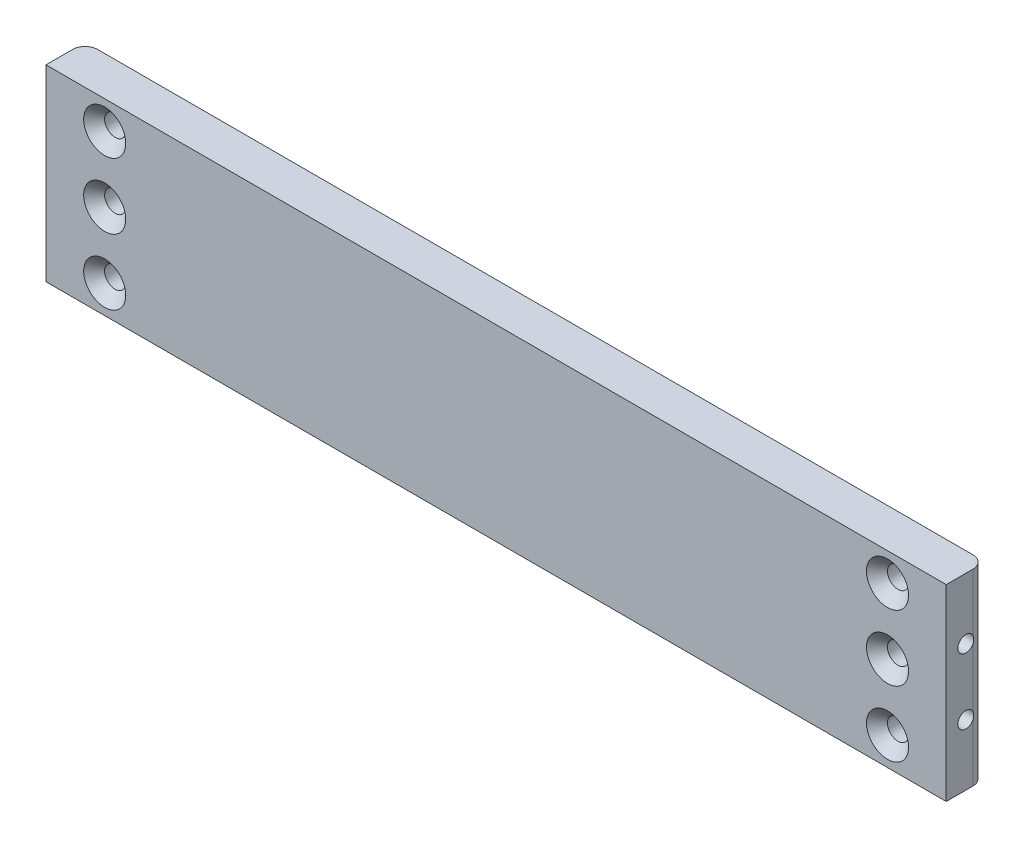
SolidWorks part; units mm, degrees
material "7075-T6 (SN)"
ref_plane "Plano frontal" through (0, 0, 0) normal (0, 0, 1) x (1, 0, 0)
ref_plane "Plano superior" through (0, 0, 0) normal (0, 1, 0) x (1, 0, 0)
ref_plane "Plano direito" through (0, 0, 0) normal (1, 0, 0) x (0, 0, -1)
sketch "Esboço1" plane through (0, 0, 0) normal (0, 0, 1) x (1, 0, 0)
  line L0 (-25, 120) -> (500, 120)
  line L1 (0, 0) -> (475, 0) construction
  line L2 (0, 0) -> (0, 120) construction
  line L3 (0, 120) -> (475, 120) construction
  line L4 (475, 0) -> (475, 120) construction
  line L5 (500, 120) -> (500, 0) construction
  line L6 (500, 0) -> (-25, 0)
  line L7 (-25, 0) -> (-25, 120) construction
  line L8 (237.5, 120) -> (237.5, 0) construction
  line L9 (-12.5, 102) -> (-12.5, 120) construction
  line L10 (-12.5, 18) -> (-12.5, 0) construction
  line L11 (-25, 120) -> (0, 120) construction
  line L12 (-25, 120) -> (0, 120) construction
  line L13 (-25, 60) -> (0, 60) construction
  line L14 (-25, 120) -> (-50, 120)
  line L15 (-50, 120) -> (-50, 0)
  line L16 (-50, 0) -> (-25, 0)
  line L17 (525, 0) -> (500, 0)
  line L18 (525, 120) -> (525, 0)
  line L19 (500, 120) -> (525, 120)
  circle A0 centre (-12.5, 102) radius 6
  circle A1 centre (-12.5, 60) radius 6
  circle A2 centre (-12.5, 18) radius 6
  circle A3 centre (487.5, 102) radius 6
  circle A4 centre (487.5, 60) radius 6
  circle A5 centre (487.5, 18) radius 6
  point P16 (-25, 60)
  point P23 (-12.5, 60)
  point P33 (0, 0)
  dimension "D5" = 12
  dimension "D1" = 525
  dimension "D2" = 120
  dimension "D3" = 25
  dimension "D4" = 25
  dimension "D6" = 18
  dimension "D7" = 25
extrude "Ressalto-extrusão1" add sketch "Esboço1" along normal blind 25 contours L0 L19 L18 L17 L6 L16 L15 L14
hole_wizard "Escareado para parafuso Allen sextavado escareado de M121" positions "Esboço2" profile "Esboço3" countersink size "M12" standard "ISO"
sketch "Esboço2" plane through (0, 0, 25) normal (0, 0, 1) x (1, 0, 0)
  point P0 (-12.5, 102)
  point P3 (-12.5, 60)
  point P6 (-12.5, 18)
  point P9 (487.5, 102)
  point P12 (487.5, 60)
  point P15 (487.5, 18)
sketch "Esboço3" plane through (-12.5, 102, 25) normal (1, 0, 0) x (0, -1, 0)
  line L0 (0, 0) -> (0, 29.0558)
  line L1 (0, 29.0558) -> (6.75, 25)
  line L2 (6.75, 25) -> (6.75, 6.69)
  line L3 (6.75, 6.69) -> (13.44, 0)
  line L5 (13.44, 0) -> (0, 0)
  line L6 (-6.75, 6.69) -> (-13.44, 0) construction
  line L10 (0, 29.0558) -> (-6.75, 25) construction
  line L11 (0, -6.35) -> (0, 107.95) construction
  dimension "Hole Dia." = 13.5
  dimension "Hole Depth" = 25
  dimension "Near C'Sink Dia." = 26.88
  dimension "Near C'Sink Angle" = 90
  dimension "Drill Angle" = 118
hole_wizard "Furo roscado de M121" positions "Esboço4" profile "Esboço6" tap size "M12" standard "ISO"
sketch "Esboço4" plane through (-50, 0, 0) normal (-1, 0, 0) x (0, 0, 1)
  line L0 (0, 60) -> (25, 60) construction
  line L1 (0, 120) -> (0, 0) construction
  line L2 (25, 120) -> (25, 0) construction
  line L4 (12.5, 60) -> (12.5, 120) construction
  line L5 (25, 120) -> (0, 120) construction
  line L6 (12.5, 60) -> (12.5, 0) construction
  line L7 (25, 0) -> (0, 0) construction
  point P0 (12.5, 81)
  point P28 (12.5, 39)
  dimension "D1" = 39
sketch "Esboço6" plane through (-50, 81, 12.5) normal (0, 1, 0) x (0, 0, 1)
  line L0 (0, 0) -> (0, 53.0644)
  line L1 (0, 53.0644) -> (5.1, 50)
  line L2 (5.1, 50) -> (5.1, 0)
  line L5 (5.1, 0) -> (0, 0)
  line L10 (0, 53.0644) -> (-5.1, 50) construction
  line L11 (0, -6.35) -> (0, 107.95) construction
  dimension "Tap Drill Dia." = 10.2
  dimension "Tap Drill Depth" = 50
  dimension "Drill Angle" = 118
cosmetic thread "Rosca de furo1" parameters "D1"=24, "D2"=12
cosmetic thread "Rosca de furo2" parameters "D1"=24, "D2"=12
ref_plane "Plano1" through (237.5, 0, 0) normal (-1, 0, 0) x (0, 0, 1)
mirror "Espelhar1" about plane through (237.5, 0, 0) normal (-1, 0, 0) of "Furo roscado de M121"
cosmetic thread "Rosca de furo3" parameters "D1"=24, "D2"=12
cosmetic thread "Rosca de furo4" parameters "D1"=24, "D2"=12
fillet "Filete1" radius 8 2 edges at (-50, 60, 0) (525, 60, 0)
